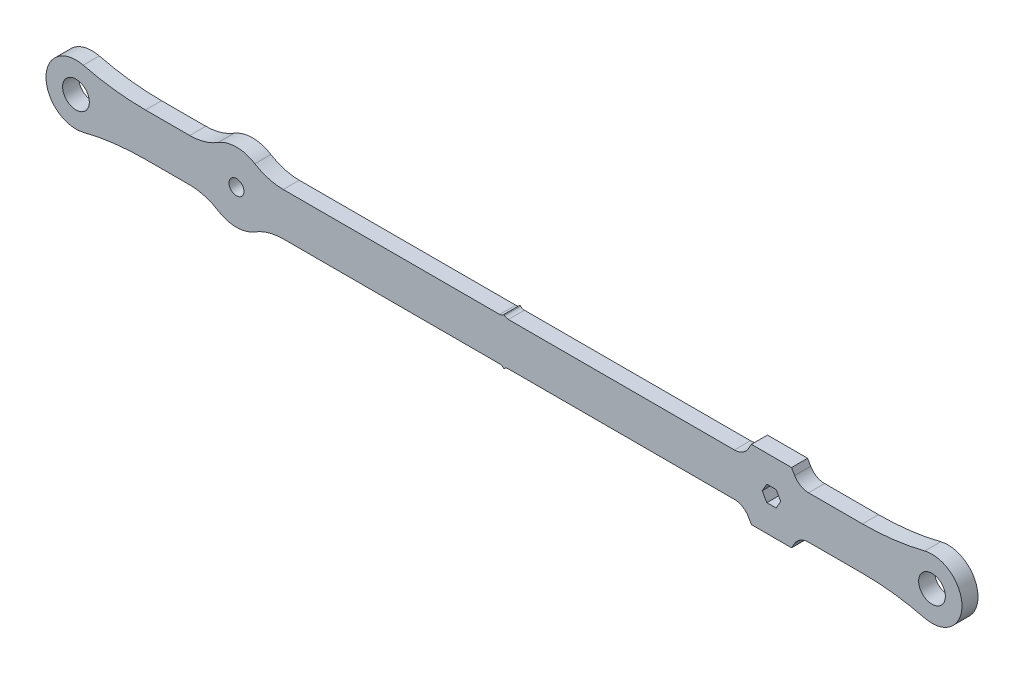
SolidWorks part; units mm, degrees
ref_plane "Front Plane" through (0, 0, 0) normal (0, 0, 1) x (1, 0, 0)
ref_plane "Top Plane" through (0, 0, 0) normal (0, 1, 0) x (1, 0, 0)
ref_plane "Right Plane" through (0, 0, 0) normal (1, 0, 0) x (0, 0, -1)
sketch "Sketch1" plane through (0, 0, 0) normal (0, 0, 1) x (1, 0, 0)
  line L0 (-80, 0) -> (80, 0) construction
  line L1 (-76.0808, -4) -> (76.0808, -4)
  line L3 (-76.0808, 4) -> (76.0808, 4)
  line L5 (-76.0808, -4) -> (76.0808, 4) construction
  line L6 (-76.0808, 4) -> (76.0808, -4) construction
  circle A0 centre (-80, 0) radius 1.5
  arc A1 (-76.0808, 4) -> (-76.0808, -4) centre (-80, 0) ccw
  circle A2 centre (80, 0) radius 1.5
  arc A3 (76.0808, -4) -> (76.0808, 4) centre (80, 0) ccw
  circle A4 centre (-64, 0) radius 1.5 construction
  circle A5 centre (64, 0) radius 1.5 construction
  point P0 (0, 0)
  point P6 (-80, 0)
  point P7 (80, 0)
  dimension "D3" = 3
  dimension "D2" = 5.6
  dimension "D5" = 3
  dimension "D1" = 160
  dimension "D4" = 8
  dimension "D6" = 16
  dimension "D7" = 16
extrude "Boss-Extrude1" add sketch "Sketch1" along normal blind 3
ref_axis "Axis2" through (80, 0, 0) along (0, 0, 1)
ref_axis "Axis3" through (-80, 0, 0) along (0, 0, 1)
sketch "Sketch3" plane through (0, 0, 0) normal (0, 1, 0) x (1, 0, 0)
  line L0 (76.0808, 0) -> (-76.0808, 0) construction
  line L1 (80, 0) -> (80, -3) construction
  line L2 (76.0808, -3) -> (85.6, -3) construction
  line L3 (-80, 0) -> (-80, -3) construction
  line L4 (80.5, 0) -> (82.4981, 0)
  line L5 (80.5, 0) -> (80.5, -3)
  line L6 (80.5, -3) -> (82.4981, -3)
  line L7 (82.4981, 0) -> (82.4981, -3)
  line L8 (82.5981, 0) -> (82.5981, -3) construction
  line L9 (85.6, 0) -> (76.0808, 0) construction
  line L10 (0, 0) -> (0, -3) construction
  line L11 (76.0808, -3) -> (-76.0808, -3) construction
  circle A0 centre (80, 1.5) radius 3 construction
  circle A1 centre (-80, 1.5) radius 3 construction
  dimension "D1" = 6
  dimension "D2" = 1.5
  dimension "D3" = 0.1
  dimension "D4" = 0.5
ref_point "Point1"
ref_point "Point2"
revolve "Cut-Revolve1" cut sketch "Sketch3" angle 360 about axis through (80, 0, 0) along (0, 0, 1)
mirror "Mirror1" about plane through (0, 0, 0) normal (1, 0, 0) of "Cut-Revolve1"
fillet "Fillet1" radius 48 4 edges at (76.0808, -4, 1.5) (76.0808, 4, 1.5) (-76.0808, -4, 1.5) (-76.0808, 4, 1.5)
sketch "Sketch4" plane through (0, 0, 3) normal (0, 0, 1) x (1, 0, 0)
  line L0 (0, -4.4) -> (0.1071, -4.2929)
  line L1 (0, -4.4) -> (-0.1071, -4.2929)
  line L2 (0.1071, 4.2929) -> (0, 4.4)
  line L3 (-0.1071, 4.2929) -> (0, 4.4)
  line L4 (0, -4.4) -> (0, 4.4) construction
  line L5 (4.4, 0) -> (-4.4, 0) construction
  line L6 (67.0015, 4) -> (-67.0015, 4) construction
  line L7 (-4.4, 4) -> (-4.4, -4)
  line L8 (-67.0015, -4) -> (67.0015, -4) construction
  line L9 (-4.4, -4) -> (-0.8142, -4)
  line L10 (4.4, -4) -> (4.4, 4)
  line L11 (4.4, 4) -> (0.8142, 4)
  line L12 (-0.8142, 4) -> (-4.4, 4)
  line L13 (0.8142, -4) -> (4.4, -4)
  arc A0 (-0.8142, -4) -> (-0.1071, -4.2929) centre (-0.8142, -5) cw
  arc A1 (0.8142, -4) -> (0.1071, -4.2929) centre (0.8142, -5) ccw
  arc A2 (0.8142, 4) -> (0.1071, 4.2929) centre (0.8142, 5) cw
  arc A3 (-0.1071, 4.2929) -> (-0.8142, 4) centre (-0.8142, 5) cw
  point P1 (0, 0)
  dimension "D2" = 1
  dimension "D1" = 0.4
extrude "Boss-Extrude3" add sketch "Sketch4" against normal through all
sketch "Sketch7" plane through (0, 0, 3) normal (0, 0, 1) x (1, 0, 0)
  line L0 (-51.25, 4) -> (-48.75, 4) construction
  line L1 (-0.8142, 4) -> (-67.0015, 4) construction
  line L2 (-51.25, 4.5) -> (-48.75, 4.5)
  line L3 (-51.25, 3.5) -> (-48.75, 3.5)
  line L4 (-51.25, -4) -> (-48.75, -4) construction
  line L5 (-67.0015, -4) -> (-0.8142, -4) construction
  line L6 (-51.25, -3.5) -> (-48.75, -3.5)
  line L7 (-51.25, -4.5) -> (-48.75, -4.5)
  arc A0 (-51.25, 4.5) -> (-51.25, 3.5) centre (-51.25, 4) ccw
  arc A1 (-48.75, 3.5) -> (-48.75, 4.5) centre (-48.75, 4) ccw
  arc A2 (-51.25, -3.5) -> (-51.25, -4.5) centre (-51.25, -4) ccw
  arc A3 (-48.75, -4.5) -> (-48.75, -3.5) centre (-48.75, -4) ccw
  point P4 (-50, 4)
  point P9 (-50, -4)
  dimension "D2" = 0.5
  dimension "D1" = 2.5
  dimension "D3" = 30
extrude "Cut-Extrude2" [suppressed] cut sketch "Sketch7" against normal through all
mirror "Mirror3" [suppressed] about plane through (0, 0, 0) normal (1, 0, 0)
sketch "Sketch8" plane through (0, 0, 3) normal (0, 0, 1) x (1, 0, 0)
  line L1 (51.7321, 0) -> (50.866, 1.5)
  line L2 (50.866, 1.5) -> (49.134, 1.5)
  line L3 (49.134, 1.5) -> (48.2679, 0)
  line L4 (48.2679, 0) -> (49.134, -1.5)
  line L5 (49.134, -1.5) -> (50.866, -1.5)
  line L6 (50.866, -1.5) -> (51.7321, 0)
  circle A0 centre (-50, 0) radius 1.4
  circle A2 centre (50, 0) radius 1.5 construction
  dimension "D1" = 2.8
  dimension "D3" = 3
  dimension "D2" = 30
  dimension "D4" = 30
extrude "Cut-Extrude3" cut sketch "Sketch8" against normal through all
sketch "Sketch9" plane through (0, 0, 3) normal (0, 0, 1) x (1, 0, 0)
  line L0 (67.0015, 4) -> (0.8142, 4) construction
  line L1 (38, -4) -> (43.0718, -4)
  line L2 (38, -4) -> (38, 4)
  line L3 (38, 4) -> (43.0718, 4)
  line L4 (62, -4) -> (62, 4)
  line L5 (38, -4) -> (62, 4) construction
  line L6 (38, 4) -> (62, -4) construction
  line L7 (56.9282, 4) -> (62, 4)
  line L8 (56.9282, -4) -> (62, -4)
  line L10 (0, -13.986) -> (0, 13.986) construction
  line L11 (-38, 4) -> (-62, -4) construction
  line L12 (-38, -4) -> (-62, 4) construction
  line L13 (-58.7321, -4) -> (-62, -4)
  line L14 (-58.7321, 4) -> (-62, 4)
  line L15 (-62, -4) -> (-62, 4)
  line L16 (-38, 4) -> (-41.2679, 4)
  line L17 (-38, -4) -> (-38, 4)
  line L18 (-38, -4) -> (-41.2679, -4)
  line L19 (-0.8142, 4) -> (-67.0015, 4) construction
  line L23 (-67.0015, -4) -> (-0.8142, -4) construction
  line L25 (54.3301, 5.5) -> (53.7528, 6.5)
  line L26 (53.7528, 6.5) -> (46.2472, 6.5)
  line L27 (46.2472, 6.5) -> (45.6699, 5.5)
  line L28 (45.6699, -5.5) -> (46.2472, -6.5)
  line L29 (46.2472, -6.5) -> (53.7528, -6.5)
  line L30 (53.7528, -6.5) -> (54.3301, -5.5)
  circle A0 centre (50, 0) radius 6.5 construction
  arc A1 (43.0718, -4) -> (45.6699, -5.5) centre (43.0718, -7) cw
  arc A2 (56.9282, -4) -> (54.3301, -5.5) centre (56.9282, -7) ccw
  arc A3 (43.0718, 4) -> (45.6699, 5.5) centre (43.0718, 7) ccw
  arc A4 (56.9282, 4) -> (54.3301, 5.5) centre (56.9282, 7) cw
  circle A6 centre (-50, 0) radius 4
  arc A7 (-46.5601, 5.5152) -> (-41.2679, 4) centre (-41.2679, 14) ccw
  arc A8 (-58.7321, 4) -> (-53.4399, 5.5152) centre (-58.7321, 14) ccw
  arc A9 (-46.5601, -5.5152) -> (-53.4399, -5.5152) centre (-50, 0) cw
  arc A10 (-53.4399, -5.5152) -> (-58.7321, -4) centre (-58.7321, -14) ccw
  circle A12 centre (50, 0) radius 4
  arc A13 (-53.4399, 5.5152) -> (-46.5601, 5.5152) centre (-50, 0) cw
  arc A14 (-41.2679, -4) -> (-46.5601, -5.5152) centre (-41.2679, -14) ccw
  dimension "D1" = 6.5
  dimension "D2" = 10
  dimension "D3" = 30
  dimension "D5" = 3
  dimension "D4" = 24
extrude "Boss-Extrude6" add sketch "Sketch9" against normal through all
ref_plane "Plane1" through (37.5, -21.6506, 0) normal (0.866, -0.5, 0) x (0, 0, -1)
ref_axis "Axis4" through (50, 0, 3.15) along (0, 0, -1)
equation "\"D7@Sketch1\"=\"D6@Sketch1\""
